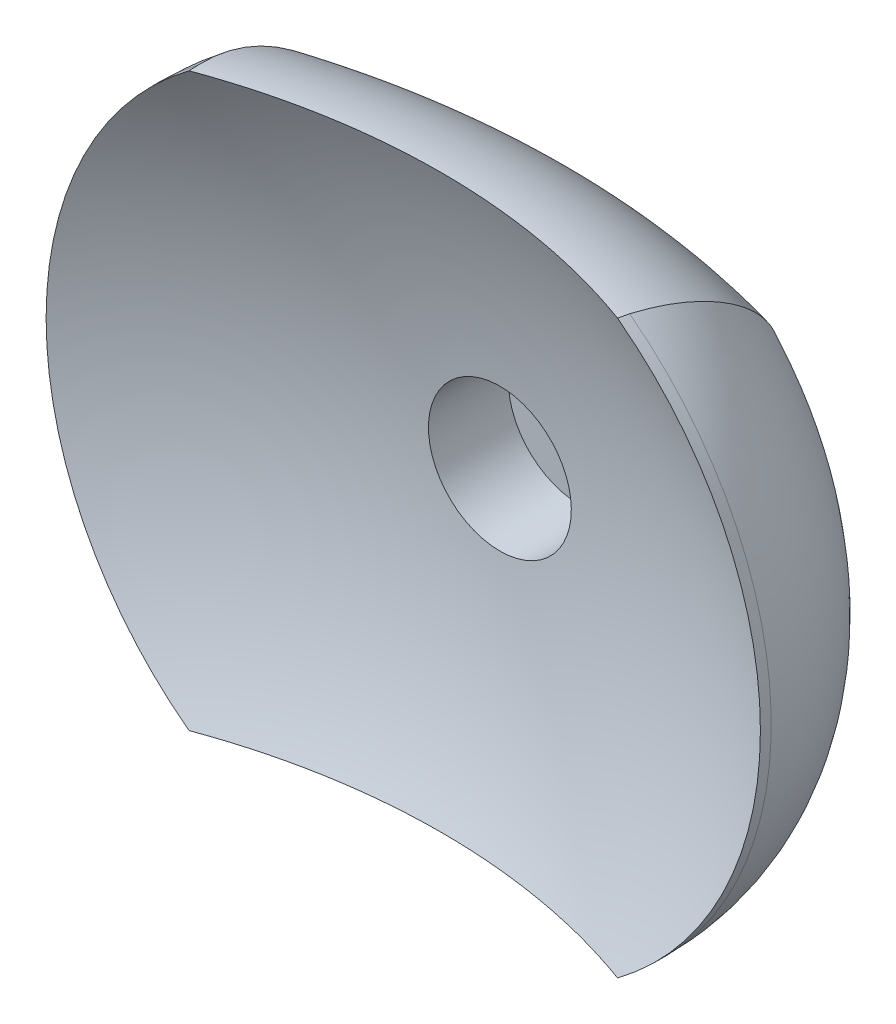
SolidWorks part; units mm, degrees
ref_plane "Front" through (0, 0, 0) normal (0, 0, 1) x (1, 0, 0)
ref_plane "Top" through (0, 0, 0) normal (0, 1, 0) x (1, 0, 0)
ref_plane "Right" through (0, 0, 0) normal (1, 0, 0) x (0, 0, -1)
sketch "ｽｹｯﾁ1" plane through (0, 0, 0) normal (1, 0, 0) x (0, 0, -1)
  line L0 (-157, 0) -> (-13, 0)
  line L1 (-25, -37.5) -> (0, -37.5)
  line L2 (-25, -37.5) -> (-25, 37.5)
  line L3 (-25, 37.5) -> (0, 37.5)
  line L4 (0, -37.5) -> (0, 37.5)
  line L5 (-12.5, 37.5) -> (-12.5, -37.5) construction
  line L6 (-25, 0) -> (0, 0)
  line L8 (-5, -7.5) -> (-45, -7.5)
  line L9 (-5, -7.5) -> (-5, 7.5)
  line L10 (-5, 7.5) -> (-45, 7.5)
  line L11 (-45, -7.5) -> (-45, 7.5)
  line L12 (-25, 7.5) -> (-25, -7.5) construction
  line L13 (-5, 0) -> (-45, 0) construction
  line L14 (0, -15) -> (-25, -15)
  line L15 (0, -15) -> (0, 15)
  line L16 (0, 15) -> (-25, 15)
  line L17 (-25, -15) -> (-25, 15)
  line L18 (-12.5, 15) -> (-12.5, -15) construction
  line L19 (0, 0) -> (-25, 0) construction
  circle A0 centre (-85, 0) radius 72
  circle A1 centre (-85, 0) radius 85
  point P2 (-12.5, 0)
  point P9 (-85, 0)
  point P13 (-12.5, 0)
  dimension "D2" = 144
  dimension "D6" = 170
  dimension "D1" = 75
  dimension "D3" = 85
  dimension "D4" = 25
  dimension "D5" = 0
  dimension "D7" = 0
  dimension "D8" = 15
  dimension "D9" = 40
  dimension "D10" = 30
revolve "回転1" add sketch "ｽｹｯﾁ1" angle 360 about L0 region at (0, 9.2112, 6.0484) region at (0, 11.2559, 0.3997) region at (0, 26.4586, 11.4597)
sketch "ｽｹｯﾁ2" plane through (0, 0, 0) normal (0, 0, 1) x (1, 0, 0)
  line L1 (-37.507, -30) -> (37.507, -30)
  line L2 (-37.507, -30) -> (-37.507, 30)
  line L3 (-37.507, 30) -> (37.507, 30)
  line L4 (37.507, -30) -> (37.507, 30)
  line L5 (0, 30) -> (0, -30) construction
  line L6 (-37.507, 0) -> (37.507, 0) construction
  circle A0 centre (0, 0) radius 37.5 construction
  circle A1 centre (0, 0) radius 37.5
  circle A2 centre (0, 0) radius 4.25
  point P0 (0, 0)
  dimension "D2" = 8.5
  dimension "D1" = 60
  dimension "75" = 75.014
extrude "ｶｯﾄ - 押し出し1" cut sketch "ｽｹｯﾁ2" along normal through all contours A2 | L3 A1 | L1 A1 region at (0, -33.0273, 0) region at (0, 33.0273, 0) region at (0, 0, 0)
fillet "ﾌｨﾚｯﾄ1" radius 20 4 edges at (0, 30, 5.4701) (0, -30, 5.4701) (-37.5, 0, 8.7193) (37.5, 0, 8.7193)
